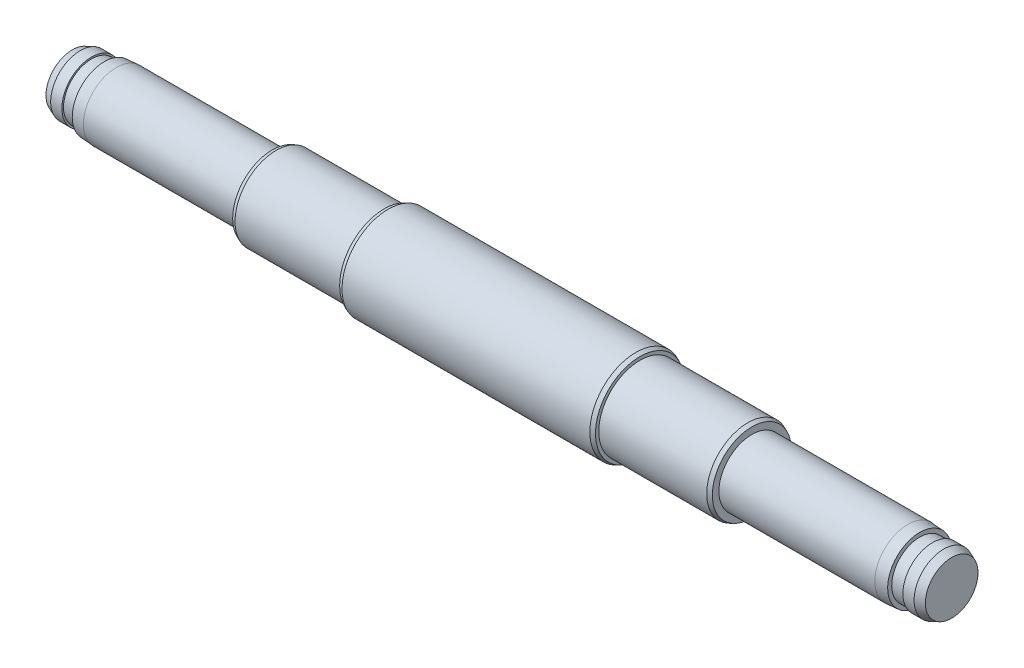
SolidWorks part; units mm, degrees
material "Простая углеродистая сталь"
ref_plane "Спереди" through (0, 0, 0) normal (0, 0, 1) x (1, 0, 0)
ref_plane "Сверху" through (0, 0, 0) normal (0, 1, 0) x (1, 0, 0)
ref_plane "Справа" through (0, 0, 0) normal (1, 0, 0) x (0, 0, -1)
sketch "Эскиз1" plane through (0, 0, 0) normal (0, 0, 1) x (1, 0, 0)
  line L0 (0, 0) -> (0, 14)
  line L1 (0, 14) -> (30, 14)
  line L2 (30, 14) -> (30, 10)
  line L3 (30, 10) -> (51, 10)
  line L4 (51, 10) -> (51, 9)
  line L5 (51, 9) -> (55, 9)
  line L6 (0, 0) -> (55, 0)
  line L7 (55, 9) -> (55, 0)
  dimension "D1" = 30
  dimension "D2" = 21
  dimension "D3" = 4
  dimension "D4" = 14
  dimension "D5" = 10
  dimension "D6" = 9
revolve "Повернуть1" add sketch "Эскиз1" angle 360 about L6
mirror "Зеркальное отражение1" about plane through (0, 0, 0) normal (1, 0, 0) of bodies 103
chamfer "Фаска1" distance 1.5 angle 10 2 edges at (51, 0, 10) (-51, 0, 10) first distance on face at (30, 0, 10) first distance on face at (-30, 0, 10)
chamfer "Фаска2" distance 1 angle 45 2 edges at (55, 0, 9) (-55, 0, 9)
sketch "Эскиз2" plane through (0, 0, 0) normal (0, 1, 0) x (1, 0, 0)
  line L1 (51, 8.5) -> (52.6, 8.5)
  line L2 (51, 8.5) -> (51, 10.9087)
  line L3 (51, 10.9087) -> (52.6, 10.9087)
  line L4 (52.6, 8.5) -> (52.6, 10.9087)
  line L5 (0, 0) -> (55, 0) construction
  line L6 (55, -8) -> (55, 8) construction
  line L8 (51, -9) -> (51, 9) construction
  dimension "D1" = 8.5
  dimension "D2" = 1.6
revolve "Вырез-Повернуть1" cut sketch "Эскиз2" angle 360 about L5
mirror "Зеркальное отражение2" about plane through (0, 0, 0) normal (1, 0, 0) of "Вырез-Повернуть1"
sketch "Эскиз3" plane through (-30, 0, 0) normal (-1, 0, 0) x (0, 0, 1)
  circle A0 centre (0, 0) radius 14 construction
  circle A1 centre (0, 0) radius 14
  circle A2 centre (0, 0) radius 12.5
  dimension "D1" = 25
extrude "Вырез-Вытянуть1" cut sketch "Эскиз3" against normal blind 14
mirror "Зеркальное отражение3" about plane through (0, 0, 0) normal (1, 0, 0) of "Вырез-Вытянуть1"
chamfer "Фаска3" distance 0.5 angle 45 2 edges at (30, 0, 12.5) (-30, 0, 12.5)
chamfer "Фаска4" distance 0.5 angle 45 2 edges at (16, 0, 14) (-16, 0, 14)
ref_axis "Ось1" through (13.175, 0, 0) along (-1, 0, 0)
scale "Scale5" scale about origin uniform scaling no x scale factor 0.85 y scale factor 0.35 z scale factor 0.35
